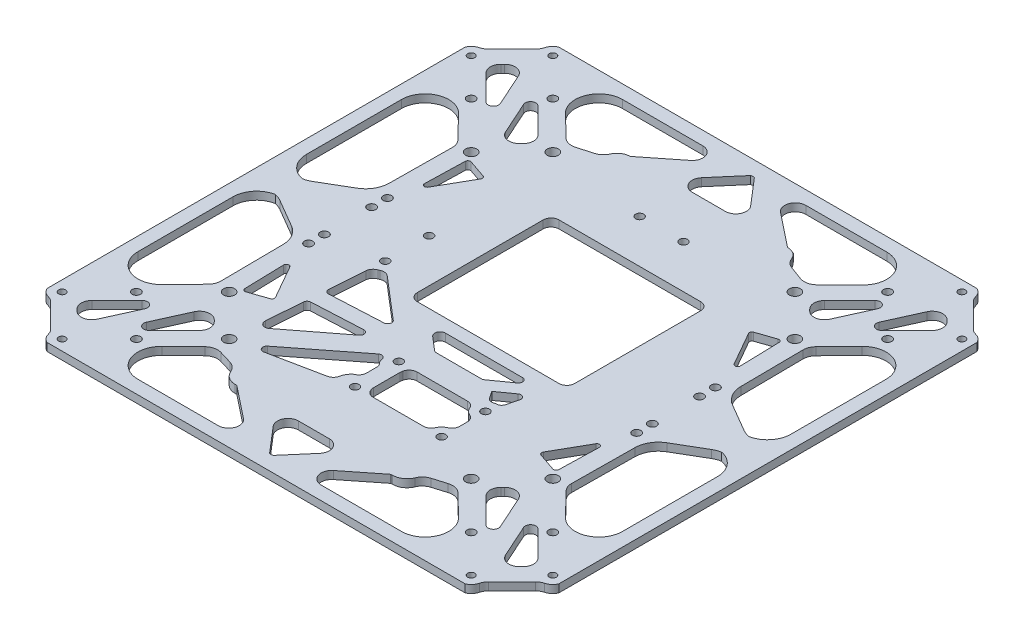
SolidWorks part; units mm, degrees
material "Thornel Mat VMA"
ref_plane "Front Plane" through (0, 0, 0) normal (0, 0, 1) x (1, 0, 0)
ref_plane "Top Plane" through (0, 0, 0) normal (0, 1, 0) x (1, 0, 0)
ref_plane "Right Plane" through (0, 0, 0) normal (1, 0, 0) x (0, 0, -1)
sketch "Sketch2" plane through (0, 0, 0) normal (0, 1, 0) x (1, 0, 0)
  line L1 (-97.5, -97.5) -> (97.5, -97.5)
  line L2 (-97.5, -97.5) -> (-97.5, 97.5)
  line L3 (-97.5, 97.5) -> (97.5, 97.5)
  line L4 (97.5, -97.5) -> (97.5, 97.5)
  line L5 (-97.5, -97.5) -> (97.5, 97.5) construction
  line L6 (-97.5, 97.5) -> (97.5, -97.5) construction
  point P0 (0, 0)
  dimension "D1" = 195
  dimension "D2" = 195
extrude "Boss-Extrude1" add sketch "Sketch2" along normal blind 3
sketch "Sketch3" plane through (0, 3, 0) normal (0, 1, 0) x (1, 0, 0)
  circle A2 centre (47.5, 41.25) radius 1.6
  circle A3 centre (47.5, -41.25) radius 1.6
  circle A4 centre (-47.5, -41.25) radius 1.6
  circle A5 centre (-47.5, 41.25) radius 1.6
  dimension "D3" = 3.2
extrude "Cut-Extrude1" cut sketch "Sketch3" against normal through all both and the other way through all
sketch "Sketch4" plane through (0, 3, 0) normal (0, 1, 0) x (1, 0, 0)
  line L4 (97.5, 97.5) -> (-97.5, 97.5) construction
  circle A0 centre (46.1238, 61.6802) radius 2.11
  circle A3 centre (-61.6802, 46.1238) radius 2.11
  circle A5 centre (-77.9437, 93.5) radius 1.35
  circle A6 centre (-93.5, 77.9437) radius 1.35
  circle A7 centre (-46.1238, 61.6802) radius 2.11
  circle A8 centre (93.5, 77.9437) radius 1.35
  circle A9 centre (77.9437, 93.5) radius 1.35
  circle A10 centre (61.6802, 46.1238) radius 2.11
  circle A11 centre (61.6802, -46.1238) radius 2.11
  circle A12 centre (77.9437, -93.5) radius 1.35
  circle A13 centre (93.5, -77.9437) radius 1.35
  circle A14 centre (-46.1238, -61.6802) radius 2.11
  circle A15 centre (-93.5, -77.9437) radius 1.35
  circle A16 centre (-77.9437, -93.5) radius 1.35
  circle A17 centre (-61.6802, -46.1238) radius 2.11
  circle A18 centre (46.1238, -61.6802) radius 2.11
  dimension "D1" = 2.7
  dimension "D3" = 4.22
  dimension "D6" = 4
extrude "Cut-Extrude2" cut sketch "Sketch4" against normal through all both and the other way through all
sketch "Sketch5" plane through (0, 3, 0) normal (0, 1, 0) x (1, 0, 0)
  circle A1 centre (30, 70) radius 2
  circle A2 centre (15, 70) radius 2
  circle A3 centre (-15, 70) radius 2
  circle A4 centre (-30, 70) radius 2
  circle A5 centre (-30, -70) radius 2
  circle A6 centre (-15, -70) radius 2
  circle A7 centre (15, -70) radius 2
  circle A8 centre (30, -70) radius 2
  dimension "D3" = 4
  dimension "D4" = 4
  dimension "D1" = 4
  dimension "D2" = 4
  dimension "D5" = 4
  dimension "D6" = 4
  dimension "D7" = 4
  dimension "D8" = 4
extrude "Cut-Extrude3" cut sketch "Sketch5" against normal through all both and the other way through all
sketch "Sketch6" plane through (0, 3, 0) normal (0, 1, 0) x (1, 0, 0)
  circle A2 centre (-62.5, 15) radius 1.6
  circle A3 centre (-62.5, -15) radius 1.6
  circle A4 centre (62.5, -15) radius 1.6
  circle A5 centre (62.5, 15) radius 1.6
  dimension "D2" = 3.2
extrude "Cut-Extrude4" cut sketch "Sketch6" against normal through all both and the other way through all
sketch "Sketch7" plane through (0, 3, 0) normal (0, 1, 0) x (1, 0, 0)
  line L0 (-68.2257, 47.6002) -> (-92.338, 72.3986)
  line L1 (-92.3432, 83.4505) -> (-83.4505, 92.3432)
  line L2 (-72.3986, 92.338) -> (-48.2358, 68.8437)
  line L3 (-43.3841, 67.6187) -> (-37.7917, 69.2071)
  line L4 (-67.1, 15) -> (-66.8107, 44.0648)
  line L5 (-30, 75) -> (-15, 75)
  line L6 (-15, 75) -> (15, 75)
  line L7 (15, 75) -> (30, 75)
  line L8 (37.5401, 69.065) -> (42.7993, 67.1289)
  line L9 (48.04, 68.2636) -> (72.4199, 92.3408)
  line L10 (83.4505, 92.3432) -> (92.3432, 83.4505)
  line L11 (68.2257, 47.6002) -> (92.338, 72.3986)
  line L12 (66.8107, 44.0648) -> (67.1, 15)
  line L13 (-67.1, -15) -> (-67.0991, 15.0916)
  line L14 (66.8107, -44.0648) -> (67.1, -15)
  line L15 (68.2257, -47.6002) -> (92.338, -72.3986)
  line L16 (83.4505, -92.3432) -> (92.3432, -83.4505)
  line L17 (48.2358, -68.8437) -> (72.3986, -92.338)
  line L18 (38.2846, -69.1587) -> (43.3041, -67.6421)
  line L19 (15, -75.5) -> (30, -75.5)
  line L20 (-15, -75.5) -> (15, -75.5)
  line L21 (-30, -75.5) -> (-15, -75.5)
  line L22 (-67.1, -15) -> (-66.8107, -44.0648)
  line L23 (-43.3041, -67.6421) -> (-38.2846, -69.1587)
  line L24 (-72.3986, -92.338) -> (-48.2358, -68.8437)
  line L25 (-92.3432, -83.4505) -> (-83.4505, -92.3432)
  line L26 (-68.2257, -47.6002) -> (-92.338, -72.3986)
  line L27 (67.0991, -15.0916) -> (67.1, 15)
  line L29 (-123.1678, -119.5363) -> (123.1678, -119.5363)
  line L30 (-123.1678, -119.5363) -> (-123.1678, 119.5363)
  line L31 (-123.1678, 119.5363) -> (123.1678, 119.5363)
  line L32 (123.1678, -119.5363) -> (123.1678, 119.5363)
  line L33 (-123.1678, -119.5363) -> (123.1678, 119.5363) construction
  line L34 (-123.1678, 119.5363) -> (123.1678, -119.5363) construction
  arc A0 (68.2257, 47.6002) -> (66.8107, 44.0648) centre (71.8104, 44.1146) ccw
  arc A1 (42.7993, 67.1289) -> (48.04, 68.2636) centre (44.5266, 71.8211) ccw
  arc A2 (37.5401, 69.065) -> (34.6337, 71.8786) centre (39.2674, 73.7571) cw
  arc A3 (-37.7917, 69.2071) -> (-34.5789, 72.0084) centre (-39.1578, 74.0168) ccw
  arc A4 (-48.2358, 68.8437) -> (-43.3841, 67.6187) centre (-44.7502, 72.4285) ccw
  arc A5 (-66.8107, 44.0648) -> (-68.2257, 47.6002) centre (-71.8104, 44.1146) ccw
  arc A6 (-92.338, 72.3986) -> (-94.6272, 73.7422) centre (-95.9228, 68.913) ccw
  arc A7 (-72.3986, 92.338) -> (-73.7422, 94.6272) centre (-68.913, 95.9228) cw
  arc A8 (-82.1505, 94.6067) -> (-83.4505, 92.3432) centre (-86.986, 95.8787) cw
  arc A9 (-92.3432, 83.4505) -> (-94.6067, 82.1505) centre (-95.8787, 86.986) cw
  arc A10 (92.338, 72.3986) -> (94.6272, 73.7422) centre (95.9228, 68.913) cw
  circle A11 centre (-93.5, 77.9437) radius 4.35
  arc A12 (-94.6067, 82.1505) -> (-94.6272, 73.7422) centre (-93.5, 77.9437) ccw
  arc A13 (92.3432, 83.4505) -> (94.6067, 82.1505) centre (95.8787, 86.986) ccw
  arc A14 (83.4505, 92.3432) -> (82.1505, 94.6067) centre (86.986, 95.8787) cw
  arc A15 (72.4199, 92.3408) -> (73.7392, 94.6158) centre (68.9065, 95.8983) ccw
  arc A16 (67.1, -15) -> (67.0991, -15.0916) centre (62.5, -15) cw
  arc A17 (-67.0991, -15.0916) -> (-67.1, -15) centre (-62.5, -15) cw
  arc A18 (94.6272, -73.7422) -> (94.6067, -82.1505) centre (93.5, -77.9437) cw
  arc A19 (82.1505, -94.6067) -> (73.7422, -94.6272) centre (77.9437, -93.5) cw
  arc A20 (35.097, -72.0664) -> (30, -75.5) centre (30, -70) cw
  circle A21 centre (-77.9437, 93.5) radius 4.35
  arc A22 (-73.7422, 94.6272) -> (-82.1505, 94.6067) centre (-77.9437, 93.5) ccw
  arc A23 (-30, -75.5) -> (-35.097, -72.0664) centre (-30, -70) cw
  arc A24 (-73.7422, -94.6272) -> (-82.1505, -94.6067) centre (-77.9437, -93.5) cw
  arc A25 (72.3986, -92.338) -> (73.7422, -94.6272) centre (68.913, -95.9228) cw
  arc A26 (83.4505, -92.3432) -> (82.1505, -94.6067) centre (86.986, -95.8787) ccw
  arc A27 (92.3432, -83.4505) -> (94.6067, -82.1505) centre (95.8787, -86.986) cw
  arc A28 (-94.6067, -82.1505) -> (-94.6272, -73.7422) centre (-93.5, -77.9437) cw
  arc A29 (92.338, -72.3986) -> (94.6272, -73.7422) centre (95.9228, -68.913) ccw
  arc A30 (-92.3432, -83.4505) -> (-94.6067, -82.1505) centre (-95.8787, -86.986) ccw
  arc A31 (-82.1505, -94.6067) -> (-83.4505, -92.3432) centre (-86.986, -95.8787) ccw
  arc A32 (-72.3986, -92.338) -> (-73.7422, -94.6272) centre (-68.913, -95.9228) ccw
  arc A33 (-92.338, -72.3986) -> (-94.6272, -73.7422) centre (-95.9228, -68.913) cw
  arc A34 (-66.8107, -44.0648) -> (-68.2257, -47.6002) centre (-71.8104, -44.1146) cw
  arc A36 (-48.2358, -68.8437) -> (-43.3041, -67.6421) centre (-44.7502, -72.4285) cw
  arc A38 (-38.2846, -69.1587) -> (-35.097, -72.0664) centre (-39.7307, -73.945) cw
  arc A39 (38.2846, -69.1587) -> (35.097, -72.0664) centre (39.7307, -73.945) ccw
  arc A43 (43.3041, -67.6421) -> (48.2358, -68.8437) centre (44.7502, -72.4285) cw
  arc A44 (68.2257, -47.6002) -> (66.8107, -44.0648) centre (71.8104, -44.1146) cw
  circle A56 centre (-30, 70) radius 5
  arc A57 (-30, 75) -> (-34.5789, 72.0084) centre (-30, 70) ccw
  circle A65 centre (30, 70) radius 5
  arc A66 (34.6337, 71.8786) -> (30, 75) centre (30, 70) ccw
  circle A74 centre (77.9437, 93.5) radius 4.35
  arc A75 (82.1505, 94.6067) -> (73.7392, 94.6158) centre (77.9437, 93.5) ccw
  circle A77 centre (93.5, 77.9437) radius 4.35
  arc A78 (94.6272, 73.7422) -> (94.6067, 82.1505) centre (93.5, 77.9437) ccw
  circle A85 centre (-62.5, 15) radius 4.6
  arc A86 (-67.0991, 15.0916) -> (-67.1, 15) centre (-62.5, 15) ccw
  circle A88 centre (62.5, 15) radius 4.6
  arc A89 (67.1, 15) -> (67.0991, 15.0916) centre (62.5, 15) ccw
  point P16 (35, 70)
  point P24 (-35, 70)
  point P39 (-93.5, 73.5937)
  point P42 (-73.5937, 93.5)
  point P53 (-82.2937, 93.5)
  point P58 (-93.5, 82.2937)
  point P61 (93.5, 73.5937)
  point P69 (93.5, 82.2937)
  point P72 (82.2937, 93.5)
  point P75 (73.5937, 93.5)
  point P76 (0, 0)
  line M55 (97.5, -97.5) -> (97.5, 97.5)
  line M56 (97.5, 97.5) -> (-97.5, 97.5)
  line M57 (-97.5, 97.5) -> (-97.5, -97.5)
  line M58 (-97.5, -97.5) -> (97.5, -97.5)
  dimension "D3" = 5
  dimension "D4" = 5
  dimension "D1" = 3
  dimension "D2" = 3
  dimension "D5" = 3
  dimension "D6" = 3
  dimension "D8" = 3
  dimension "D11" = 3
  dimension "D14" = 3
  dimension "D15" = 3
extrude "Cut-Extrude5" cut sketch "Sketch7" against normal through all both and the other way through all contours A86 L4 A5 L0 A6 A12 A28 A33 L26 A34 L22 A17 L13 M57 | A24 A31 L25 A30 A28 M57 M58 | L29 L32 L31 L30 A78 A18 A19 A24 A28 A12 A22 A75 M55 M58 M57 M56 | A43 L18 A39 A20 L19 L20 L21 A23 A38 L23 A36 L24 A32 A24 A19 A25 L17 M58 | A89 L27 L14 A16 A44 L15 A29 A18 A78 A10 L11 A0 L12 M55 | A27 L16 A26 A19 A18 M58 M55 | A75 A22 A7 L2 A4 L3 A3 A57 L5 L6 L7 A66 A2 L8 A1 L9 A15 M56 | A22 A12 A9 L1 A8 M56 M57 | A78 A75 A14 L10 A13 M55 M56 region at (-83.5018, 3, 0) region at (-91.2706, 3, -91.2706) region at (-91.2706, 3, 91.2706) region at (0.1643, 3, -85.7939) region at (0, 3, 85.9801) region at (91.2706, 3, -91.2706) region at (91.2706, 3, 91.2706) region at (83.5018, 3, 0) region at (-119.7351, 3, 0) body kept at (-79.6532, 0, 97.5)
sketch "Sketch8" plane through (0, 3, 0) normal (0, 1, 0) x (1, 0, 0)
  line L14 (-46.0759, -21.349) -> (-46.0759, 21.3635)
  line L23 (56.1243, 4.2494) -> (47.983, 21.7846)
  line L24 (-47.9835, -21.7689) -> (-56.1299, -4.1605)
  line L25 (-56.1243, 4.2494) -> (-47.983, 21.7846)
  line L26 (47.9835, -21.7689) -> (56.1299, -4.1605)
  line L27 (46.0759, -21.349) -> (46.0759, 21.3635)
  line L30 (-58.3187, 26.3483) -> (-51.0349, 39.095)
  line L31 (-51.5781, 40.5368) -> (-58.4638, 42.9035)
  line L32 (-59.7885, 41.9842) -> (-60.1866, 26.8708)
  line L33 (-59.7885, -41.9842) -> (-60.1866, -26.8708)
  line L35 (59.7885, 41.9842) -> (60.1866, 26.8708)
  line L36 (51.5781, 40.5368) -> (58.4638, 42.9035)
  line L37 (58.3187, 26.3483) -> (51.0349, 39.095)
  line L38 (-51.5781, -40.5368) -> (-58.4638, -42.9035)
  line L39 (-58.3187, -26.3483) -> (-51.0349, -39.095)
  line L40 (58.3187, -26.3483) -> (51.0349, -39.095)
  line L41 (51.5781, -40.5368) -> (58.4638, -42.9035)
  line L42 (59.7885, -41.9842) -> (60.1866, -26.8708)
  line L43 (-29.1909, -41.25) -> (-22, -41.25)
  line L44 (-15, -48.25) -> (-15, -58)
  line L46 (-22, -65) -> (-23.2561, -65)
  line L47 (-29.2355, -61.6396) -> (-35.1703, -51.8896)
  line L48 (29.1909, 41.25) -> (22, 41.25)
  line L50 (29.2355, -61.6396) -> (35.1703, -51.8896)
  line L51 (22, -65) -> (23.2561, -65)
  line L52 (15, -48.25) -> (15, -58)
  line L53 (29.1909, -41.25) -> (22, -41.25)
  line L54 (15, 48.25) -> (15, 58)
  line L55 (22, 65) -> (23.2561, 65)
  line L56 (29.2355, 61.6396) -> (35.1703, 51.8896)
  line L57 (-29.2355, 61.6396) -> (-35.1703, 51.8896)
  line L58 (-22, 65) -> (-23.2561, 65)
  line L59 (-15, 48.25) -> (-15, 58)
  line L60 (-29.1909, 41.25) -> (-22, 41.25)
  line L64 (-55.3178, 58.1431) -> (-54.6091, 58.8518)
  line L65 (-54.6091, 64.5086) -> (-64.2157, 74.1152)
  line L66 (-84.3061, 81.4807) -> (-85.0147, 80.7721)
  line L67 (-85.0147, 75.1152) -> (-75.4082, 65.5087)
  line L68 (55.3178, -58.1431) -> (54.6091, -58.8518)
  line L69 (-77.8313, 80.2967) -> (-72.1708, 67.7451)
  line L70 (-67.453, 71.8787) -> (-61.7925, 59.3271)
  line L71 (-32.5, -18.2077) -> (-14.5052, -3.0601)
  line L72 (67.453, 71.8787) -> (61.7925, 59.3271)
  line L73 (77.8313, 80.2967) -> (72.1708, 67.7451)
  line L74 (85.0147, 75.1152) -> (75.4082, 65.5087)
  line L75 (84.3061, 81.4807) -> (85.0147, 80.7721)
  line L76 (54.6091, 64.5086) -> (64.2157, 74.1152)
  line L77 (55.3178, 58.1431) -> (54.6091, 58.8518)
  line L78 (54.6091, -64.5086) -> (64.2157, -74.1152)
  line L79 (84.3061, -81.4807) -> (85.0147, -80.7721)
  line L80 (85.0147, -75.1152) -> (75.4082, -65.5087)
  line L81 (77.8313, -80.2967) -> (72.1708, -67.7451)
  line L82 (67.453, -71.8787) -> (61.7925, -59.3271)
  line L83 (-67.453, -71.8787) -> (-61.7925, -59.3271)
  line L84 (-77.8313, -80.2967) -> (-72.1708, -67.7451)
  line L85 (-85.0147, -75.1152) -> (-75.4082, -65.5087)
  line L86 (-84.3061, -81.4807) -> (-85.0147, -80.7721)
  line L87 (-54.6091, -64.5086) -> (-64.2157, -74.1152)
  line L88 (-55.3178, -58.1431) -> (-54.6091, -58.8518)
  line L89 (-32.5, 18.2077) -> (-14.5052, 3.0601)
  line L90 (-39.0759, -15.1476) -> (-39.0759, 15.1476)
  line L91 (-20.3144, 26.25) -> (-2.5759, 11.3182)
  line L92 (2.5759, 11.3182) -> (20.3144, 26.25)
  line L93 (-17.7385, 33.3101) -> (17.7385, 33.3101)
  line L94 (32.5, -18.2077) -> (14.5052, -3.0601)
  line L95 (39.0759, 15.1476) -> (39.0759, -15.1476)
  line L96 (14.5052, 3.0601) -> (32.5, 18.2077)
  line L97 (17.7385, -33.3101) -> (-17.7385, -33.3101)
  line L98 (-20.3144, -26.25) -> (-2.5759, -11.3182)
  line L99 (20.3144, -26.25) -> (2.5759, -11.3182)
  circle A13 centre (0, 0) radius 3
  arc A14 (-46.0759, -21.349) -> (-47.9835, -21.7689) centre (-47.0759, -21.349) cw
  arc A15 (-46.0759, 21.3635) -> (-47.983, 21.7846) centre (-47.0759, 21.3635) ccw
  arc A16 (-56.1299, -4.1605) -> (-56.1243, 4.2494) centre (-47.0542, 0.0383) cw
  arc A17 (56.1299, -4.1605) -> (56.1243, 4.2494) centre (47.0542, 0.0383) ccw
  arc A18 (46.0759, 21.3635) -> (47.983, 21.7846) centre (47.0759, 21.3635) cw
  arc A19 (46.0759, -21.349) -> (47.9835, -21.7689) centre (47.0759, -21.349) ccw
  arc A20 (-58.3187, 26.3483) -> (-60.1866, 26.8708) centre (-59.187, 26.8445) cw
  arc A21 (-51.0349, 39.095) -> (-51.5781, 40.5368) centre (-51.9032, 39.5911) ccw
  arc A22 (-58.4638, 42.9035) -> (-59.7885, 41.9842) centre (-58.7889, 41.9578) ccw
  arc A23 (58.4638, 42.9035) -> (59.7885, 41.9842) centre (58.7889, 41.9578) cw
  arc A24 (51.0349, 39.095) -> (51.5781, 40.5368) centre (51.9032, 39.5911) cw
  arc A25 (58.3187, 26.3483) -> (60.1866, 26.8708) centre (59.187, 26.8445) ccw
  arc A26 (-58.4638, -42.9035) -> (-59.7885, -41.9842) centre (-58.7889, -41.9578) cw
  arc A27 (-51.0349, -39.095) -> (-51.5781, -40.5368) centre (-51.9032, -39.5911) cw
  arc A28 (-58.3187, -26.3483) -> (-60.1866, -26.8708) centre (-59.187, -26.8445) ccw
  arc A29 (58.3187, -26.3483) -> (60.1866, -26.8708) centre (59.187, -26.8445) cw
  arc A30 (51.0349, -39.095) -> (51.5781, -40.5368) centre (51.9032, -39.5911) ccw
  arc A31 (58.4638, -42.9035) -> (59.7885, -41.9842) centre (58.7889, -41.9578) ccw
  arc A32 (-15, -48.25) -> (-22, -41.25) centre (-22, -48.25) ccw
  arc A33 (-29.1909, -41.25) -> (-35.1703, -51.8896) centre (-29.1909, -48.25) ccw
  arc A34 (-29.2355, -61.6396) -> (-23.2561, -65) centre (-23.2561, -58) ccw
  arc A35 (-15, -58) -> (-22, -65) centre (-22, -58) cw
  arc A36 (15, -58) -> (22, -65) centre (22, -58) ccw
  arc A37 (29.2355, -61.6396) -> (23.2561, -65) centre (23.2561, -58) cw
  arc A38 (29.1909, -41.25) -> (35.1703, -51.8896) centre (29.1909, -48.25) cw
  arc A39 (15, -48.25) -> (22, -41.25) centre (22, -48.25) cw
  arc A40 (15, 48.25) -> (22, 41.25) centre (22, 48.25) ccw
  arc A41 (29.1909, 41.25) -> (35.1703, 51.8896) centre (29.1909, 48.25) ccw
  arc A42 (29.2355, 61.6396) -> (23.2561, 65) centre (23.2561, 58) ccw
  arc A43 (15, 58) -> (22, 65) centre (22, 58) cw
  arc A44 (-15, 58) -> (-22, 65) centre (-22, 58) ccw
  arc A45 (-29.2355, 61.6396) -> (-23.2561, 65) centre (-23.2561, 58) cw
  arc A46 (-29.1909, 41.25) -> (-35.1703, 51.8896) centre (-29.1909, 48.25) cw
  arc A47 (-15, 48.25) -> (-22, 41.25) centre (-22, 48.25) cw
  arc A48 (-55.3178, 58.1431) -> (-61.7925, 59.3271) centre (-58.1462, 60.9716) cw
  arc A49 (-54.6091, 58.8518) -> (-54.6091, 64.5086) centre (-57.4376, 61.6802) ccw
  arc A50 (-77.8313, 80.2967) -> (-84.3061, 81.4807) centre (-81.4777, 78.6523) ccw
  arc A51 (-85.0147, 80.7721) -> (-85.0147, 75.1152) centre (-82.1863, 77.9437) ccw
  arc A52 (-64.2157, 74.1152) -> (-67.453, 71.8787) centre (-65.6299, 72.7009) ccw
  arc A53 (-72.1708, 67.7451) -> (-75.4082, 65.5087) centre (-73.994, 66.9229) cw
  arc A54 (72.1708, 67.7451) -> (75.4082, 65.5087) centre (73.994, 66.9229) ccw
  arc A55 (64.2157, 74.1152) -> (67.453, 71.8787) centre (65.6299, 72.7009) cw
  arc A56 (85.0147, 80.7721) -> (85.0147, 75.1152) centre (82.1863, 77.9437) cw
  arc A57 (77.8313, 80.2967) -> (84.3061, 81.4807) centre (81.4777, 78.6523) cw
  arc A58 (54.6091, 58.8518) -> (54.6091, 64.5086) centre (57.4376, 61.6802) cw
  arc A59 (55.3178, 58.1431) -> (61.7925, 59.3271) centre (58.1462, 60.9716) ccw
  arc A60 (55.3178, -58.1431) -> (61.7925, -59.3271) centre (58.1462, -60.9716) cw
  arc A61 (54.6091, -58.8518) -> (54.6091, -64.5086) centre (57.4376, -61.6802) ccw
  arc A62 (77.8313, -80.2967) -> (84.3061, -81.4807) centre (81.4777, -78.6523) ccw
  arc A63 (85.0147, -80.7721) -> (85.0147, -75.1152) centre (82.1863, -77.9437) ccw
  arc A64 (64.2157, -74.1152) -> (67.453, -71.8787) centre (65.6299, -72.7009) ccw
  arc A65 (72.1708, -67.7451) -> (75.4082, -65.5087) centre (73.994, -66.9229) cw
  arc A66 (-72.1708, -67.7451) -> (-75.4082, -65.5087) centre (-73.994, -66.9229) ccw
  arc A67 (-64.2157, -74.1152) -> (-67.453, -71.8787) centre (-65.6299, -72.7009) cw
  arc A68 (-85.0147, -80.7721) -> (-85.0147, -75.1152) centre (-82.1863, -77.9437) cw
  arc A69 (-77.8313, -80.2967) -> (-84.3061, -81.4807) centre (-81.4777, -78.6523) cw
  arc A70 (-54.6091, -58.8518) -> (-54.6091, -64.5086) centre (-57.4376, -61.6802) cw
  arc A71 (-55.3178, -58.1431) -> (-61.7925, -59.3271) centre (-58.1462, -60.9716) ccw
  arc A84 (-20.3144, 26.25) -> (-17.7385, 33.3101) centre (-17.7385, 29.3101) cw
  arc A85 (-2.5759, 11.3182) -> (2.5759, 11.3182) centre (0, 14.3784) ccw
  arc A86 (20.3144, 26.25) -> (17.7385, 33.3101) centre (17.7385, 29.3101) ccw
  arc A87 (39.0759, 15.1476) -> (32.5, 18.2077) centre (35.0759, 15.1476) ccw
  arc A88 (14.5052, -3.0601) -> (14.5052, 3.0601) centre (17.0811, 0) cw
  arc A89 (32.5, -18.2077) -> (39.0759, -15.1476) centre (35.0759, -15.1476) ccw
  arc A90 (17.7385, -33.3101) -> (20.3144, -26.25) centre (17.7385, -29.3101) ccw
  arc A91 (-2.5759, -11.3182) -> (2.5759, -11.3182) centre (0, -14.3784) cw
  arc A92 (-17.7385, -33.3101) -> (-20.3144, -26.25) centre (-17.7385, -29.3101) cw
  arc A93 (-32.5, -18.2077) -> (-39.0759, -15.1476) centre (-35.0759, -15.1476) cw
  arc A94 (-14.5052, -3.0601) -> (-14.5052, 3.0601) centre (-17.0811, 0) ccw
  arc A95 (-32.5, 18.2077) -> (-39.0759, 15.1476) centre (-35.0759, 15.1476) ccw
  point P50 (-58.0759, 0.0458)
  point P61 (58.0759, 0.0458)
  dimension "D1" = 4
  dimension "D4" = 1
  dimension "D5" = 10
  dimension "D6" = 1
  dimension "D7" = 7
  dimension "D8" = 4
  dimension "D9" = 2
  dimension "D3" = 12
extrude "Cut-Extrude7" cut sketch "Sketch8" against normal through all both and the other way through all
sketch "Sketch9" plane through (0, 0, 0) normal (0, 1, 0) x (1, 0, 0)
  line L0 (-76.2341, 97.5) -> (76.2341, 97.5)
  line L1 (-97.5, 76.2341) -> (-92.338, 76.2341)
  line L2 (-97.5, 76.2341) -> (-97.5, -76.2341)
  line L3 (-97.5, -76.2341) -> (-92.338, -76.2341)
  line L4 (-92.338, 76.2341) -> (-92.338, -76.2341)
  line L5 (-72.3986, 92.338) -> (75.7801, 92.338)
  line L6 (92.338, 76.2341) -> (92.338, -76.2341)
  line L7 (97.5, -76.2341) -> (92.338, -76.2341)
  line L8 (97.5, 76.2341) -> (97.5, -76.2341)
  line L9 (97.5, 76.2341) -> (92.338, 76.2341)
  line L11 (75.7801, 92.338) -> (76.2341, 97.5)
  line L12 (-76.2341, 97.5) -> (-74.9539, 93.3918)
  line L13 (-74.9539, 93.3918) -> (-72.3986, 92.338)
  line L15 (-74.9539, -93.3918) -> (-72.3986, -92.338)
  line L16 (-76.2341, -97.5) -> (-74.9539, -93.3918)
  line L17 (75.7801, -93.3918) -> (76.2341, -97.5)
  line L18 (72.3986, -92.338) -> (75.7801, -93.3918)
  line L19 (-72.3986, -92.338) -> (72.3986, -92.338)
  line L20 (-76.2341, -97.5) -> (76.2341, -97.5)
extrude "Boss-Extrude2" add sketch "Sketch9" along normal up to surface (3 mm away) up to face at (56.578, 3, 36.2456)
fillet "Fillet1" radius 9 8 edges at (-72.3986, 1.5, 92.338) (-92.338, 1.5, 72.3986) (92.338, 1.5, 72.3986) (72.3986, 1.5, 92.338) (92.338, 1.5, -72.3986) (72.4171, 1.5, -92.338) (-72.3986, 1.5, -92.338) (-92.338, 1.5, -72.3986)
sketch "Sketch10" plane through (0, 0, 0) normal (0, -1, 0) x (1, 0, 0)
  line L0 (0.1317, -92.338) -> (15, -75)
  line L1 (50.4957, -92.338) -> (-50.2322, -92.338) construction
  line L2 (-30, -75) -> (30, -75) construction
  line L3 (15, -75) -> (30, -75)
  line L4 (30, -75) -> (8.1317, -92.338)
  line L5 (8.1317, -92.338) -> (0.1317, -92.338)
  line L7 (-8.1317, -92.338) -> (-0.1317, -92.338)
  line L8 (-30, -75) -> (-8.1317, -92.338)
  line L9 (-15, -75) -> (-30, -75)
  line L10 (-0.1317, -92.338) -> (-15, -75)
  line L11 (-0.1317, 92.338) -> (-15, 75)
  line L12 (-15, 75) -> (-30, 75)
  line L13 (-30, 75) -> (-8.1317, 92.338)
  line L14 (-8.1317, 92.338) -> (-0.1317, 92.338)
  line L15 (8.1317, 92.338) -> (0.1317, 92.338)
  line L16 (30, 75) -> (8.1317, 92.338)
  line L17 (15, 75) -> (30, 75)
  line L18 (0.1317, 92.338) -> (15, 75)
  line L23 (0, 0) -> (0, 24.1776) construction
  line L36 (-92.338, -5) -> (-84.338, -5)
  line L37 (-92.338, 5) -> (-84.338, 5)
  line L38 (-84.338, 5) -> (-67.0991, 15.0916)
  line L39 (-67.0991, 15.0916) -> (-67.0991, -15.0916)
  line L40 (-67.0991, -15.0916) -> (-84.338, -5)
  line L41 (-92.338, 5) -> (-92.338, -5)
  line L42 (92.338, 5) -> (92.338, -5)
  line L43 (67.0991, -15.0916) -> (84.338, -5)
  line L44 (67.0991, 15.0916) -> (67.0991, -15.0916)
  line L45 (84.338, 5) -> (67.0991, 15.0916)
  line L46 (92.338, 5) -> (84.338, 5)
  line L47 (92.338, -5) -> (84.338, -5)
  dimension "D1" = 8
extrude "Boss-Extrude3" add sketch "Sketch10" against normal up to surface (3 mm away) contours L7 L10 L9 L8 | L5 L4 L3 L0 | L39 | L15 L18 L17 L16 | L14 L13 L12 L11 | L41 L36 L40 L39 L38 L37 | L42 L47 L43 L44 L45 L46 region at (14.2476, 0, -82.7895) region at (-14.2476, 0, -82.7895) region at (-14.2476, 0, 82.7895) region at (14.2476, 0, 82.7895) up to face at (0, 3, 74.8987)
fillet "Fillet2" radius 9 12 edges at (84.338, 1.5, 5) (92.338, 1.5, 5) (67.0991, 1.5, 15.0916) (84.338, 1.5, -5) (92.338, 1.5, -5) (67.0991, 1.5, -15.0916) (-84.338, 1.5, 5) (-92.338, 1.5, 5) (-84.338, 1.5, -5) (-92.338, 1.5, -5) (-67.0991, 1.5, -15.0916) (-67.0991, 1.5, 15.0916)
fillet "Fillet3" radius 4 8 edges at (14.5712, 1.5, 75.5) (-14.5712, 1.5, 75.5) (-8.1317, 1.5, 92.338) (8.1317, 1.5, 92.338) (-15, 1.5, -75) (15, 1.5, -75) (8.1317, 1.5, -92.338) (-8.1317, 1.5, -92.338)
sketch "Sketch11" plane through (0, 0, 0) normal (0, -1, 0) x (1, 0, 0)
  line L0 (-1.5025, 92.338) -> (1.4975, 92.338)
  line L1 (-1.5025, 91.838) -> (-1.5025, 90.838) construction
  line L2 (0, 0) -> (117.3836, 0) construction
  line L3 (1.4975, 91.838) -> (1.4975, 90.838) construction
  line L4 (-2.0025, 92.338) -> (1.9975, 92.338) construction
  line L5 (-1.5025, -92.338) -> (-1.5025, -90.838)
  line L6 (1.4975, 92.338) -> (1.4975, 90.838)
  line L7 (1.4975, -92.338) -> (1.4975, -90.838)
  line L8 (-1.5025, 92.338) -> (-1.5025, 90.838)
  line L9 (-1.5025, 91.838) -> (1.4975, 91.838) construction
  line L10 (-2.0025, 92.338) -> (-2.0025, 90.838) construction
  line L11 (-1.5025, -92.338) -> (1.4975, -92.338)
  line L14 (1.9975, 92.338) -> (1.9975, 90.838) construction
  arc A0 (-1.5025, 90.838) -> (1.4975, 90.838) centre (-0.0025, 90.1655) cw
  arc A1 (-1.5025, -90.838) -> (1.4975, -90.838) centre (-0.0025, -90.1655) ccw
  point P3 (-0.0025, 92.338)
  point P19 (-0.0025, -92.338)
  dimension "D4" = 0.5
extrude "Boss-Extrude4" add sketch "Sketch11" against normal up to surface (3 mm away) up to face at (78.3031, 3, -28.8709)
sketch "Sketch12" plane through (0, 0, 0) normal (0, 1, 0) x (1, 0, 0)
  line L1 (-34.1125, -65.173) -> (33.0728, -65.173)
  line L2 (-34.1125, -65.173) -> (-34.1125, -72.502)
  line L3 (-34.1125, -72.502) -> (33.0728, -72.502)
  line L4 (33.0728, -65.173) -> (33.0728, -72.502)
  line L5 (-32.7348, 74.1858) -> (33.0728, 74.1858)
  line L6 (-32.7348, 74.1858) -> (-32.7348, 66.5049)
  line L7 (-32.7348, 66.5049) -> (33.0728, 66.5049)
  line L8 (33.0728, 74.1858) -> (33.0728, 66.5049)
  arc A0 (-30, 75) -> (-34.5789, 72.0084) centre (-30, 70) ccw construction
extrude "Boss-Extrude5" add sketch "Sketch12" along normal up to surface (3 mm away) up to face at (0.0007, 3, 82.7847)
sketch "Sketch13" plane through (0, 3, 0) normal (0, 1, 0) x (1, 0, 0)
  line L0 (-97.5, 79.6532) -> (-97.5, -79.6532) construction
  circle A0 centre (-62.5, 9) radius 1.6
  circle A3 centre (-62.5, 15) radius 1.6 construction
  circle A4 centre (-62.5, -9) radius 1.6
  circle A5 centre (62.5, -9) radius 1.6
  circle A6 centre (62.5, 9) radius 1.6
  dimension "D1" = 3.2
  dimension "D2" = 35
  dimension "D3" = 6
extrude "Cut-Extrude8" cut sketch "Sketch13" against normal through all both and the other way through all
sketch "Sketch14" plane through (0, 3, 0) normal (0, 1, 0) x (1, 0, 0)
  line L1 (-49.7531, -38.4774) -> (-42.6685, -38.4774)
  line L2 (-49.7531, -38.4774) -> (-49.7531, -44.7981)
  line L3 (-49.7531, -44.7981) -> (-42.6685, -44.7981)
  line L4 (-42.6685, -38.4774) -> (-42.6685, -44.7981)
  line L5 (43.2252, -37.3262) -> (50.4701, -37.3262)
  line L6 (43.2252, -37.3262) -> (43.2252, -44.7981)
  line L7 (43.2252, -44.7981) -> (50.4701, -44.7981)
  line L8 (50.4701, -37.3262) -> (50.4701, -44.7981)
  line L9 (-49.7531, 45.318) -> (-42.6685, 45.318)
  line L10 (-49.7531, 45.318) -> (-49.7531, 37.98)
  line L11 (-49.7531, 37.98) -> (-42.6685, 37.98)
  line L12 (-42.6685, 45.318) -> (-42.6685, 37.98)
  line L13 (43.2252, 45.318) -> (50.4701, 45.318)
  line L14 (43.2252, 45.318) -> (43.2252, 35.8323)
  line L15 (43.2252, 35.8323) -> (50.4701, 35.8323)
  line L16 (50.4701, 45.318) -> (50.4701, 35.8323)
extrude "Boss-Extrude6" add sketch "Sketch14" against normal up to surface (3 mm away) up to face at (62.5, 0, -10.6)
sketch "Sketch15" plane through (0, 0, 0) normal (0, 1, 0) x (1, 0, 0)
  line L1 (38.1112, -67.172) -> (-38.039, -67.172)
  line L2 (38.1112, -67.172) -> (38.1112, -38.1498)
  line L3 (38.1112, -38.1498) -> (-38.039, -38.1498)
  line L4 (-38.039, -67.172) -> (-38.039, -38.1498)
  line L5 (58.5626, -23.0556) -> (26.3059, -23.0556)
  line L6 (58.5626, -23.0556) -> (58.5626, 24.5465)
  line L7 (58.5626, 24.5465) -> (26.3059, 24.5465)
  line L8 (-57.9373, -23.0556) -> (-57.9373, 24.5465)
  line L9 (26.3059, -35.8956) -> (-27.2465, -35.8956)
  line L10 (26.3059, -35.8956) -> (26.3059, -23.0556)
  line L12 (-27.2465, -35.8956) -> (-27.2465, -23.0556)
  line L13 (26.3059, 38.0129) -> (40.0854, 38.0129)
  line L14 (-41.6524, 38.0129) -> (-27.2465, 38.0129)
  line L15 (-41.6524, 38.0129) -> (-41.6524, 66.5116)
  line L16 (-41.6524, 66.5116) -> (40.0854, 66.5116)
  line L17 (40.0854, 38.0129) -> (40.0854, 66.5116)
  line L18 (-27.2465, -23.0556) -> (-57.9373, -23.0556)
  line L19 (-27.2465, 24.5465) -> (-27.2465, 38.0129)
  line L20 (-27.2465, 24.5465) -> (-57.9373, 24.5465)
  line L21 (26.3059, 24.5465) -> (26.3059, 38.0129)
extrude "Boss-Extrude7" add sketch "Sketch15" along normal up to surface (3 mm away) up to face at (62.5, 3, -10.6)
sketch "Sketch16" plane through (0, 3, 0) normal (0, 1, 0) x (1, 0, 0)
  line L0 (34.4, 40.5) -> (-25.6, 40.5)
  line L1 (34.4, 40.5) -> (34.4, -13.5)
  line L2 (34.4, -13.5) -> (-25.6, -13.5)
  line L3 (-25.6, 40.5) -> (-25.6, -13.5)
  line L4 (-97.5, 79.6532) -> (-97.5, -79.6532) construction
  line L5 (79.6532, 97.5) -> (-79.6532, 97.5) construction
  dimension "D1" = 71.9
  dimension "D2" = 54
  dimension "D3" = 57
  dimension "D4" = 60
extrude "Cut-Extrude9" cut sketch "Sketch16" against normal through all both and the other way through all
fillet "Fillet4" radius 3 4 edges at (-25.6, 1.5, 13.5) (-25.6, 1.5, -40.5) (34.4, 1.5, 13.5) (34.4, 1.5, -40.5)
sketch "Sketch17" plane through (0, 3, 0) normal (0, 1, 0) x (1, 0, 0)
  line L0 (-25.6, -10.5) -> (-25.6, 37.5) construction
  line L2 (-22.6, 40.5) -> (31.4, 40.5) construction
  circle A0 centre (-42.1, 10.5) radius 1.55
  circle A1 centre (-42.1, -6.21) radius 1.55
  circle A2 centre (-6.3762, -36.746) radius 1.55
  circle A3 centre (-6.3762, -53.456) radius 1.55
  circle A4 centre (26.6238, -36.746) radius 1.55
  circle A5 centre (26.6238, -53.456) radius 1.55
  circle A6 centre (8.355, 57.0021) radius 1.55
  circle A7 centre (-8.355, 57) radius 1.55
  circle A8 centre (46.1238, -61.6802) radius 2.11 construction
  dimension "D2" = 3.1
  dimension "D3" = 3.1
  dimension "D7" = 3.1
  dimension "D8" = 3.1
  dimension "D13" = 3.1
  dimension "D14" = 3.1
  dimension "D18" = 3.1
  dimension "D19" = 3.1
  dimension "D1" = 16.71
  dimension "D4" = 16.5
  dimension "D5" = 33
  dimension "D6" = 16.71
  dimension "D9" = 30
  dimension "D10" = 33
  dimension "D11" = 19.5
  dimension "D12" = 16.71
  dimension "D17" = 16.71
  dimension "D20" = 16.5
  dimension "D21" = 8.355
extrude "Cut-Extrude10" cut sketch "Sketch17" against normal up to surface (3 mm away) up to face at (4.4, 0, -13.5)
sketch "Sketch18" plane through (0, 3, 0) normal (0, 1, 0) x (1, 0, 0)
  circle A0 centre (-63.8015, 79.3579) radius 1.6
  circle A2 centre (-77.9437, 93.5) radius 1.35 construction
  circle A3 centre (-79.3579, 63.8015) radius 1.6
  circle A4 centre (79.3579, 63.8015) radius 1.6
  circle A5 centre (63.8015, 79.3579) radius 1.6
  circle A6 centre (63.8015, -79.3579) radius 1.6
  circle A7 centre (79.3579, -63.8015) radius 1.6
  circle A8 centre (-79.3579, -63.8015) radius 1.6
  circle A9 centre (-63.8015, -79.3579) radius 1.6
  dimension "D1" = 3.2
  dimension "D3" = 20
extrude "Cut-Extrude11" cut sketch "Sketch18" against normal through all both and the other way through all
sketch "Sketch20" plane through (0, 3, 0) normal (0, 1, 0) x (1, 0, 0)
  line L0 (-8.2133, -22.0203) -> (-5.1452, -24.6428)
  line L1 (-2.5449, -40.1931) -> (-2.5449, -50.2481)
  line L2 (26.6238, -46.5277) -> (26.6238, -43.6744)
  line L3 (19.6955, -36.746) -> (0.5522, -36.746)
  line L4 (0.5522, -53.456) -> (19.6955, -53.456)
  line L5 (15.5846, -26.746) -> (0.5522, -26.746)
  line L6 (0.5522, -26.746) -> (-1.9464, -26.746)
  line L7 (-5.1452, -24.6428) -> (-3.2459, -26.2663)
  line L8 (-45.1914, -48.8264) -> (-44.211, -35.3108)
  line L9 (-36.8334, -10.7118) -> (-21.0302, -24.2201)
  line L10 (-8.7158, -42.9523) -> (-8.7158, -46.6929)
  line L11 (-15.1397, -55.2627) -> (-35.2638, -59.3592)
  line L12 (-30.3359, -3.1103) -> (-5.1452, -24.6428) construction
  line L13 (23.0717, -31.6191) -> (21.1858, -28.8971)
  line L16 (28.2033, -30.7121) -> (29.3469, -26.3434)
  line L17 (19.6955, -26.746) -> (0.5522, -26.746) construction
  line L18 (-6.9138, -18.5) -> (22.4781, -18.5)
  line L19 (-36.4864, -56.7072) -> (-12.7584, -38.1723)
  line L20 (-41.9764, -50.5556) -> (-22.6039, -35.6368)
  line L21 (-21.929, -26.8584) -> (-41.983, -27.8727)
  line L22 (-36.8334, -10.7118) -> (-11.6427, -32.2443) construction
  line L23 (-23.5949, -32.9503) -> (-42.7907, -33.9212)
  line L24 (21.0253, -29.0113) -> (27.0261, -24.7414)
  line L25 (-43.5549, -26.2661) -> (-42.6013, -13.1202)
  line L26 (15.5846, -26.746) -> (23.3477, -21.2222)
  arc A0 (26.377, -32.2027) -> (25.2983, -32.3934) centre (26.6238, -36.746) ccw
  arc A2 (-12.7584, -52.6714) -> (-15.1397, -55.2627) centre (-15.7381, -52.323) cw
  arc A5 (26.377, -32.2027) -> (28.2033, -30.7121) centre (26.2685, -30.2057) ccw
  arc A6 (-8.7158, -46.6929) -> (-10.6687, -49.5043) centre (-11.7158, -46.6929) cw
  arc A8 (25.2983, -32.3934) -> (23.0717, -31.6191) centre (24.7157, -30.4801) cw
  arc A9 (-9.1442, -41.4073) -> (-8.7158, -42.9523) centre (-11.7158, -42.9523) cw
  arc A11 (-40.1008, -10.2973) -> (-36.8334, -10.7118) centre (-38.7827, -12.9922) cw
  arc A12 (-40.5989, -10.5052) -> (-42.6013, -13.1202) centre (-39.6091, -13.3373) ccw
  arc A17 (-3.2459, -26.2663) -> (-1.9464, -26.746) centre (-1.9464, -24.746) ccw
  arc A19 (-2.4543, -39.4613) -> (-2.3985, -39.2048) centre (-6.3687, -38.4767) ccw
  arc A20 (-2.1824, -51.6896) -> (-2.2457, -51.5541) centre (-7.3016, -53.9988) ccw
  arc A21 (24.8159, -49.2807) -> (26.6238, -46.5277) centre (23.6238, -46.5277) ccw
  arc A23 (24.8159, -49.2807) -> (22.4485, -51.6481) centre (26.6238, -53.456) ccw
  arc A24 (22.4485, -38.554) -> (24.8159, -40.9214) centre (26.6238, -36.746) ccw
  arc A25 (24.8159, -40.9214) -> (26.6238, -43.6744) centre (23.6238, -43.6744) cw
  arc A27 (-10.6687, -49.5043) -> (-12.7584, -52.6714) centre (-7.3016, -53.9988) ccw
  arc A28 (-10.354, -39.1166) -> (-9.1442, -41.4073) centre (-6.3687, -38.4767) ccw
  arc A29 (-2.2457, -51.5541) -> (-2.5449, -50.2481) centre (0.4551, -50.2481) cw
  arc A30 (-2.4543, -39.4613) -> (-2.5449, -40.1931) centre (0.4551, -40.1931) ccw
  arc A31 (-41.9764, -50.5556) -> (-45.1914, -48.8264) centre (-43.1967, -48.9711) cw
  arc A33 (-2.3985, -39.2048) -> (0.5522, -36.746) centre (0.5522, -39.746) cw
  arc A34 (22.4485, -38.554) -> (19.6955, -36.746) centre (19.6955, -39.746) ccw
  circle A35 centre (-42.1, -6.21) radius 4.55
  arc A36 (-40.5989, -10.5052) -> (-40.1008, -10.2973) centre (-42.1, -6.21) ccw
  arc A37 (22.4485, -51.6481) -> (19.6955, -53.456) centre (19.6955, -50.456) cw
  arc A38 (-2.1824, -51.6896) -> (0.5522, -53.456) centre (0.5522, -50.456) ccw
  arc A39 (-8.2133, -22.0203) -> (-6.9138, -18.5) centre (-6.9138, -20.5) cw
  arc A41 (-35.2638, -59.3592) -> (-36.4864, -56.7072) centre (-35.563, -57.8893) cw
  arc A42 (-12.7584, -38.1723) -> (-10.354, -39.1166) centre (-11.835, -39.3544) cw
  arc A43 (-21.0302, -24.2201) -> (-21.929, -26.8584) centre (-22.0048, -25.3603) cw
  arc A44 (-23.5949, -32.9503) -> (-22.6039, -35.6368) centre (-23.5191, -34.4484) cw
  arc A45 (-42.7907, -33.9212) -> (-44.211, -35.3108) centre (-42.7149, -35.4193) ccw
  arc A46 (-43.5549, -26.2661) -> (-41.983, -27.8727) centre (-42.0588, -26.3746) ccw
  arc A47 (22.4781, -18.5) -> (23.3477, -21.2222) centre (22.4781, -20) cw
  arc A48 (29.3469, -26.3434) -> (27.0261, -24.7414) centre (27.8958, -25.9636) ccw
  point P75 (19.6955, -26.746)
  dimension "D5" = 3
  dimension "D6" = 10
  dimension "D1" = 3
  dimension "D2" = 3
  dimension "D10" = 2
  dimension "D3" = 2
  dimension "D11" = 1.5
  dimension "D12" = 1.5
  dimension "D9" = 1.5
  dimension "D13" = 1.5
  dimension "D8" = 19.1432
  dimension "D4" = 3
  dimension "D7" = 10
extrude "Cut-Extrude12" cut sketch "Sketch20" against normal through all both and the other way through all contours A47 L18 A39 L0 L7 A17 L6 L5 L26 | A20 A38 L4 A37 A23 A21 L2 A25 A24 A34 L3 A33 A19 A30 L1 A29 | L16 A48 L24 L13 A8 A0 A5 | A42 L19 A41 L11 A2 A27 A6 L10 A9 A28 | L23 A45 L8 A31 L20 A44 | L25 A46 L21 A43 L9 A11 A36 A12 region at (7.1077, 3, 22.2399) region at (11.1558, 3, 45.1016) region at (-36.2549, 3, 39.9084) region at (-34.5196, 3, 20.6864) region at (-20.2393, 3, 49.9427) region at (25.7962, 3, 28.7122)
